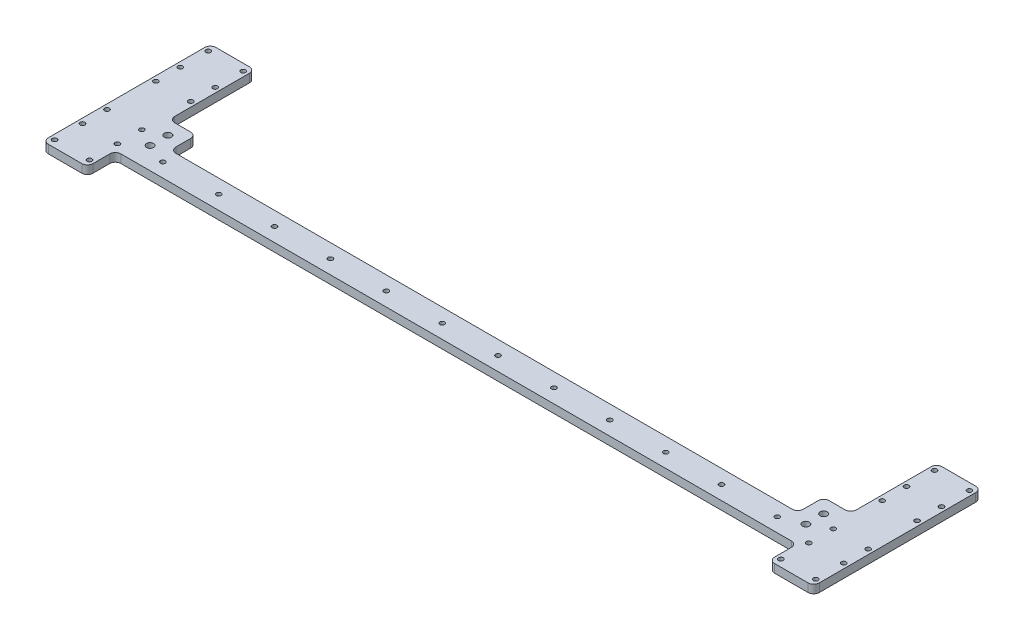
SolidWorks part; units mm, degrees
ref_plane "Front Plane" through (0, 0, 0) normal (0, 0, 1) x (1, 0, 0)
ref_plane "Top Plane" through (0, 0, 0) normal (0, 1, 0) x (1, 0, 0)
ref_plane "Right Plane" through (0, 0, 0) normal (1, 0, 0) x (0, 0, -1)
sketch "Sketch1" plane through (0, 0, 0) normal (0, 1, 0) x (1, 0, 0)
  line L1 (0, 0) -> (552, 0)
  line L2 (0, 0) -> (0, 20)
  line L3 (0, 20) -> (552, 20)
  line L4 (552, 0) -> (552, 20)
  dimension "D1" = 20
  dimension "D2" = 552
extrude "Boss-Extrude1" add sketch "Sketch1" along normal blind 6
ref_plane "Plane1" through (276, 0, 0) normal (1, 0, 0) x (0, 0, -1)
sketch "Sketch3" plane through (0, 0, 0) normal (0, -1, 0) x (1, 0, 0)
  line L0 (0, 0) -> (552, 0) construction
  line L1 (0, -100) -> (32, -100)
  line L2 (0, -100) -> (0, 20)
  line L3 (0, 20) -> (32, 20)
  line L4 (32, -100) -> (32, 20)
  dimension "D1" = 32
  dimension "D2" = 120
  dimension "D3" = 20
extrude "Boss-Extrude2" add sketch "Sketch3" against normal up to surface (6 mm away) up to face at (276, 6, -10)
sketch "Sketch4" plane through (0, 6, 0) normal (0, 1, 0) x (1, 0, 0)
  line L0 (16, -20) -> (16, 100)
  line L1 (0, -20) -> (32, -20) construction
  line L2 (32, 100) -> (0, 100) construction
  line L4 (3.5, -15) -> (28.5, -15)
  line L5 (3.5, -15) -> (3.5, 5)
  line L6 (3.5, 5) -> (28.5, 5)
  line L7 (28.5, -15) -> (28.5, 5)
  line L8 (3.5, -15) -> (28.5, 5) construction
  line L9 (3.5, 5) -> (28.5, -15) construction
  line L10 (3.5, 75) -> (28.5, 75)
  line L11 (3.5, 75) -> (3.5, 95)
  line L12 (3.5, 95) -> (28.5, 95)
  line L13 (28.5, 75) -> (28.5, 95)
  line L14 (3.5, 75) -> (28.5, 95) construction
  line L15 (3.5, 95) -> (28.5, 75) construction
  line L16 (28.5, 57.5) -> (3.5, 57.5)
  line L17 (28.5, 57.5) -> (28.5, 22.5)
  line L18 (28.5, 22.5) -> (3.5, 22.5)
  line L19 (3.5, 57.5) -> (3.5, 22.5)
  line L20 (28.5, 57.5) -> (3.5, 22.5) construction
  line L21 (28.5, 22.5) -> (3.5, 57.5) construction
  point P6 (16, -5)
  point P11 (16, 85)
  point P16 (16, 40)
  dimension "D1" = 20
  dimension "D2" = 25
  dimension "D3" = 5
  dimension "D4" = 5
  dimension "D5" = 35
  dimension "D6" = 25
sketch "Sketch7" plane through (0, 6, 0) normal (0, 1, 0) x (1, 0, 0)
  line L0 (276, 0) -> (276, 20) construction
  line L1 (32, 0) -> (552, 0) construction
  line L2 (552, 20) -> (32, 20) construction
  line L3 (276, -3.3) -> (276, 3.3) construction
  line L4 (276, 10) -> (256, 10) construction
  point P11 (256, 10)
  point P13 (216, 10)
  point P14 (176, 10)
  point P15 (136, 10)
  point P16 (96, 10)
  point P17 (56, 10)
  dimension "D1" = 20
  dimension "D3" = 40
  dimension "D2" = 6
hole_wizard "M3 Clearance Hole1" positions "Sketch5" profile "Sketch6" hole size "M3" standard "ANSI Metric" end condition through all
sketch "Sketch5" plane through (0, 6, 0) normal (0, 1, 0) x (1, 0, 0)
  point P0 (3.5, -15)
  point P3 (3.5, 5)
  point P6 (28.5, 5)
  point P9 (28.5, -15)
  point P12 (3.5, 95)
  point P15 (28.5, 95)
  point P18 (28.5, 75)
  point P21 (3.5, 75)
  point P25 (56, 10)
  point P28 (96, 10)
  point P31 (136, 10)
  point P34 (176, 10)
  point P37 (216, 10)
  point P40 (256, 10)
  point P43 (28.5, 57.5)
  point P46 (28.5, 22.5)
  point P49 (3.5, 22.5)
  point P52 (3.5, 57.5)
sketch "Sketch6" plane through (3.5, 6, 15) normal (1, 0, 0) x (0, 0, 1)
  line L0 (0, 0) -> (0, 6)
  line L1 (0, 6) -> (1.7, 6)
  line L2 (1.7, 6) -> (1.7, 0)
  line L5 (1.7, 0) -> (0, 0)
  line L11 (0, -6.35) -> (0, 107.95) construction
  dimension "Thru Hole Dia." = 3.4
  dimension "Thru Hole Depth" = 6
sketch "Sketch8" plane through (0, 6, 0) normal (0, 1, 0) x (1, 0, 0)
  line L0 (56.3721, 22) -> (87.6482, 22) construction
  line L1 (552, 20) -> (32, 20) construction
  line L2 (105.1095, -2) -> (88.5975, -2) construction
  line L3 (32, 0) -> (552, 0) construction
  line L4 (34.8662, 100) -> (34.8662, 28.3662) construction
  line L5 (34.8662, -20) -> (34.8662, -8.3662) construction
  line L6 (28.5, -20) -> (28.5, 100) construction
  line L7 (0, -20) -> (32, -20) construction
  line L8 (32, 100) -> (0, 100) construction
  line L9 (28.5, 75) -> (28.5, 95) construction
  circle A0 centre (41.2324, 28.3662) radius 6.3662
  circle A1 centre (28.5, 100) radius 6.3662
  circle A2 centre (28.5, -20) radius 6.3662
  circle A3 centre (41.2324, -8.3662) radius 6.3662
  circle A4 centre (41.2324, 28.3662) radius 10.16
  circle A5 centre (41.2324, -8.3662) radius 10.16
  circle A6 centre (28.5, -20) radius 10.16
  circle A7 centre (28.5, 100) radius 10.16
  dimension "D3" = 12.7324
  dimension "D4" = 20.32
  dimension "D1" = 2
  dimension "D2" = 2
sketch "Sketch10" plane through (0, 6, 0) normal (0, 1, 0) x (1, 0, 0)
  line L5 (32, 20) -> (51.3924, 20)
  line L6 (32, 20) -> (32, 38.5262)
  line L7 (32, 38.5262) -> (51.3924, 38.5262)
  line L8 (51.3924, 20) -> (51.3924, 38.5262)
  circle A2 centre (41.2324, 28.3662) radius 2.525
  dimension "D1" = 5.05
  dimension "D2" = 18.5262
  dimension "D3" = 19.3924
extrude "Boss-Extrude3" add sketch "Sketch10" against normal up to surface (6 mm away) up to face at (3.5, 0, 16.7)
sketch "Sketch12" plane through (0, 6, 0) normal (0, 1, 0) x (1, 0, 0)
  line L0 (41.2324, 28.3662) -> (41.2324, 15.6362) construction
  circle A0 centre (41.2324, 15.6362) radius 2.525
  circle A2 centre (41.2324, 28.3662) radius 2.525 construction
  dimension "D1" = 12.73
extrude "Cut-Extrude2" cut sketch "Sketch12" against normal through all
fillet "Fillet2" radius 4 8 edges at (32, 3, 20) (0, 3, 20) (0, 3, -100) (32, 3, -100) (32, 3, -38.5262) (51.3924, 3, -38.5262) (51.3924, 3, -20) (32, 3, 0)
mirror "Mirror1" about plane through (276, 0, 0) normal (1, 0, 0) of "Cut-Extrude2", "Boss-Extrude2", "M3 Clearance Hole1", "Boss-Extrude3", "Fillet2"
